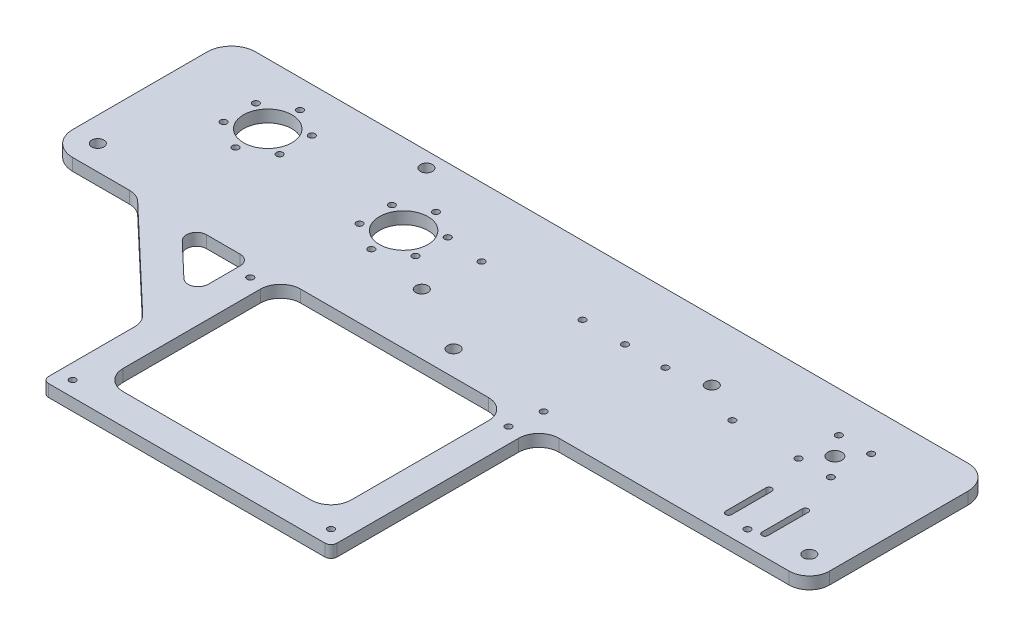
SolidWorks part; units mm, degrees
material "Policarbonato"
ref_plane "Plano frontal" through (0, 0, 0) normal (0, 0, 1) x (1, 0, 0)
ref_plane "Plano superior" through (0, 0, 0) normal (0, 1, 0) x (1, 0, 0)
ref_plane "Plano direito" through (0, 0, 0) normal (1, 0, 0) x (0, 0, -1)
sketch "Esboço1" plane through (0, 0, 0) normal (0, 1, 0) x (1, 0, 0)
  line L3 (-85.5279, -153.6487) -> (51.4721, -153.6487)
  line L4 (54.4721, -150.6487) -> (54.4721, -60.6487)
  line L6 (188.5279, -40.6487) -> (188.5279, 28)
  line L7 (176.5279, 40) -> (-176.5279, 40)
  line L8 (-188.5279, 28) -> (-188.5279, -38.6487)
  line L9 (-176.5279, -50.6487) -> (-148.4656, -50.6487)
  line L10 (-141.5771, -53.3996) -> (-91.6394, -100.8535)
  line L11 (-88.5279, -108.1025) -> (-88.5279, -150.6487)
  line L12 (-110.1764, -50.6487) -> (-93.5279, -50.6487)
  line L13 (-88.5279, -55.6487) -> (-88.5279, -71.4691)
  line L14 (-96.9722, -75.0936) -> (-113.6207, -59.2732)
  line L15 (39.4721, -60.6487) -> (39.4721, -128.6487)
  line L16 (29.4721, -138.6487) -> (-63.5279, -138.6487)
  line L17 (-73.5279, -128.6487) -> (-73.5279, -60.6487)
  line L18 (-63.5279, -50.6487) -> (29.4721, -50.6487)
  line L20 (132.5279, 0) -> (148.5279, 0) construction
  line L21 (132.5279, 0) -> (132.5279, 20) construction
  line L22 (132.5279, 20) -> (148.5279, 20) construction
  line L23 (148.5279, 0) -> (148.5279, 20) construction
  line L24 (132.5279, 0) -> (148.5279, 20) construction
  line L25 (132.5279, 20) -> (148.5279, 0) construction
  line L30 (64.4721, -50.6487) -> (178.5279, -50.6487)
  line L31 (156.5279, -40.6487) -> (156.5279, -20.6487) construction
  line L32 (155.0279, -40.6487) -> (155.0279, -20.6487)
  line L33 (158.0279, -40.6487) -> (158.0279, -20.6487)
  line L34 (147.5279, -45.2211) -> (147.5279, -21.4375) construction
  line L36 (138.5279, -40.6487) -> (138.5279, -20.6487) construction
  line L37 (140.0279, -40.6487) -> (140.0279, -20.6487)
  line L38 (137.0279, -40.6487) -> (137.0279, -20.6487)
  line L39 (49.2221, -43) -> (150.2221, -43) construction
  line L40 (54.4721, -120.5) -> (144.9721, -120.5) construction
  line L41 (54.4721, -120.5) -> (54.4721, -7) construction
  line L42 (54.4721, -7) -> (144.9721, -7) construction
  line L43 (144.9721, -120.5) -> (144.9721, -7) construction
  line L44 (54.4721, -120.5) -> (144.9721, -7) construction
  line L45 (54.4721, -7) -> (144.9721, -120.5) construction
  circle A0 centre (-81.0279, -58.1487) radius 1.6
  circle A1 centre (-81.0279, -146.1487) radius 1.6
  circle A2 centre (46.9721, -58.1487) radius 1.6
  circle A3 centre (46.9721, -146.1487) radius 1.6
  circle A8 centre (176.311, -38.4318) radius 3
  circle A9 centre (0, -38.4318) radius 3
  circle A11 centre (-140.5279, 10) radius 12
  circle A20 centre (-140.5279, 10) radius 16 construction
  circle A21 centre (-140.5279, -6) radius 1.6
  circle A22 centre (-154.3843, 2) radius 1.6
  circle A23 centre (-154.3843, 18) radius 1.6
  circle A24 centre (-84.3674, 32.5) radius 3
  circle A25 centre (-176.311, -38.4318) radius 3
  circle A26 centre (140.5279, 10) radius 3.5
  circle A27 centre (148.5279, 0) radius 1.6
  circle A28 centre (148.5279, 20) radius 1.6
  circle A29 centre (132.5279, 0) radius 1.6
  circle A30 centre (132.5279, 20) radius 1.6
  arc A31 (51.4721, -153.6487) -> (54.4721, -150.6487) centre (51.4721, -150.6487) ccw
  arc A34 (188.5279, 28) -> (176.5279, 40) centre (176.5279, 28) ccw
  arc A35 (-176.5279, 40) -> (-188.5279, 28) centre (-176.5279, 28) ccw
  arc A36 (-188.5279, -38.6487) -> (-176.5279, -50.6487) centre (-176.5279, -38.6487) ccw
  arc A37 (-91.6394, -100.8535) -> (-88.5279, -108.1025) centre (-98.5279, -108.1025) cw
  arc A38 (-88.5279, -150.6487) -> (-85.5279, -153.6487) centre (-85.5279, -150.6487) ccw
  arc A39 (-93.5279, -50.6487) -> (-88.5279, -55.6487) centre (-93.5279, -55.6487) cw
  arc A40 (-88.5279, -71.4691) -> (-96.9722, -75.0936) centre (-93.5279, -71.4691) cw
  arc A41 (-113.6207, -59.2732) -> (-110.1764, -50.6487) centre (-110.1764, -55.6487) cw
  arc A42 (39.4721, -128.6487) -> (29.4721, -138.6487) centre (29.4721, -128.6487) cw
  arc A43 (-63.5279, -138.6487) -> (-73.5279, -128.6487) centre (-63.5279, -128.6487) cw
  arc A44 (-73.5279, -60.6487) -> (-63.5279, -50.6487) centre (-63.5279, -60.6487) cw
  arc A45 (29.4721, -50.6487) -> (39.4721, -60.6487) centre (29.4721, -60.6487) cw
  circle A46 centre (-140.5279, 26) radius 1.6
  circle A47 centre (-126.6715, 18) radius 1.6
  circle A48 centre (-126.6715, 2) radius 1.6
  circle A49 centre (-63.1716, 0) radius 16 construction
  circle A50 centre (-63.1716, -16) radius 1.6
  circle A51 centre (-77.028, -8) radius 1.6
  circle A52 centre (-77.028, 8) radius 1.6
  circle A53 centre (-63.1716, 16) radius 1.6
  circle A54 centre (-49.3152, 8) radius 1.6
  circle A55 centre (-49.3152, -8) radius 1.6
  circle A56 centre (-63.1716, 0) radius 12
  circle A57 centre (-33.5279, -20.6487) radius 3
  circle A58 centre (79.5279, 10) radius 3
  arc A61 (-148.4656, -50.6487) -> (-141.5771, -53.3996) centre (-148.4656, -60.6487) cw
  arc A62 (188.5279, -40.6487) -> (178.5279, -50.6487) centre (178.5279, -40.6487) cw
  arc A63 (54.4721, -60.6487) -> (64.4721, -50.6487) centre (64.4721, -60.6487) cw
  arc A64 (155.0279, -40.6487) -> (158.0279, -40.6487) centre (156.5279, -40.6487) ccw
  arc A65 (158.0279, -20.6487) -> (155.0279, -20.6487) centre (156.5279, -20.6487) ccw
  arc A66 (140.0279, -40.6487) -> (137.0279, -40.6487) centre (138.5279, -40.6487) cw
  arc A67 (137.0279, -20.6487) -> (140.0279, -20.6487) centre (138.5279, -20.6487) cw
  circle A68 centre (99.7221, 0) radius 1.6
  circle A69 centre (49.2221, -43) radius 1.6
  circle A70 centre (150.2221, -43) radius 1.6
  circle A71 centre (-30.5279, 6) radius 1.6
  circle A72 centre (19.4721, 6) radius 1.6
  circle A73 centre (60.5279, 6) radius 1.6
  circle A75 centre (40.5279, 6) radius 1.6
  point P14 (156.5279, -30.6487)
  point P43 (-140.5279, 10)
  point P70 (-144.4721, -50.6487)
  point P116 (-63.1716, 0)
  point P123 (0, 40)
  point P124 (138.5279, -30.6487)
  point P129 (99.7221, -63.75)
  point P135 (99.7221, -7)
  point P141 (99.7221, -43)
  dimension "D2" = 3
  dimension "D7" = 10
  dimension "D8" = 12
  dimension "D10" = 90.6487
  dimension "D11" = 61
  dimension "D12" = 203.9448
  dimension "D13" = 7.5
  dimension "D14" = 104.1605
  dimension "D16" = 12
  dimension "D20" = 10
  dimension "D21" = 3
  dimension "D22" = 48.4318
  dimension "D23" = 32
  dimension "D24" = 3.2
  dimension "D25" = 6
  dimension "D26" = 24
  dimension "D27" = 48
  dimension "D28" = 30
  dimension "D29" = 40
  dimension "D30" = 6
  dimension "D34" = 30
  dimension "D31" = 32
  dimension "D32" = 3.2
  dimension "D33" = 24
  dimension "D35" = 6
  dimension "D36" = 155
  dimension "D37" = 30
  dimension "D44" = 7
  dimension "D48" = 10
  dimension "D54" = 143
  dimension "D6" = 10
  dimension "D58" = 5
  dimension "D62" = 1.5
  dimension "D68" = 101
  dimension "D72" = 80
  dimension "D1" = 137
  dimension "D9" = 377.0558
  dimension "D15" = 66.6487
  dimension "D17" = 32.0558
  dimension "D18" = 100
  dimension "D19" = 42.5462
  dimension "D38" = 48
  dimension "D39" = 15
  dimension "D40" = 12.2169
  dimension "D41" = 12.2169
  dimension "D42" = 16
  dimension "D43" = 20
  dimension "D45" = 15
  dimension "D46" = 15
  dimension "D47" = 15
  dimension "D49" = 7.5
  dimension "D50" = 7.5
  dimension "D51" = 88
  dimension "D52" = 128
  dimension "D53" = 93
  dimension "D55" = 15
  dimension "D56" = 20.6487
  dimension "D57" = 68
  dimension "D59" = 32
  dimension "D60" = 10
  dimension "D61" = 20
  dimension "D63" = 9
  dimension "D64" = 113.5
  dimension "D65" = 90.5
  dimension "D66" = 7
  dimension "D67" = 43
  dimension "D69" = 34
  dimension "D70" = 110
  dimension "D71" = 50
  dimension "D73" = 20
extrude "Ressalto-extrusão1" add sketch "Esboço1" against normal blind 6
